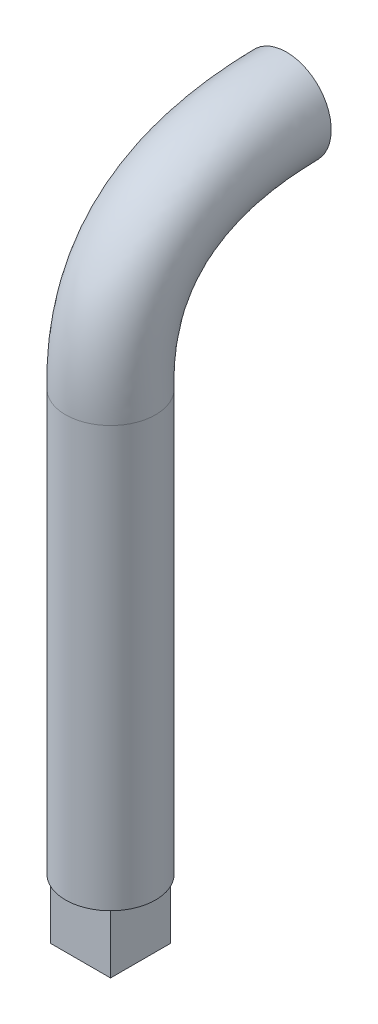
SolidWorks part; units mm, degrees
ref_plane "Front Plane" through (0, 0, 0) normal (0, 0, 1) x (1, 0, 0)
ref_plane "Top Plane" through (0, 0, 0) normal (0, 1, 0) x (1, 0, 0)
ref_plane "Right Plane" through (0, 0, 0) normal (1, 0, 0) x (0, 0, -1)
sketch "Sketch1" plane through (0, 0, 0) normal (0, 1, 0) x (1, 0, 0)
  circle A0 centre (0, 0) radius 7.5
extrude "Boss-Extrude1" add sketch "Sketch1" along normal blind 70
sketch "Sketch2" plane through (0, 0, 0) normal (0, -1, 0) x (1, 0, 0)
  line L1 (-5, 5) -> (5, 5)
  line L2 (-5, 5) -> (-5, -5)
  line L3 (-5, -5) -> (5, -5)
  line L4 (5, 5) -> (5, -5)
  line L5 (-5, 5) -> (5, -5) construction
  line L6 (-5, -5) -> (5, 5) construction
  point P0 (0, 0)
extrude "Boss-Extrude2" add sketch "Sketch2" along normal blind 10
sketch "Sketch3" plane through (0, 0, 0) normal (1, 0, 0) x (0, 0, -1)
  line L0 (7.5, 70) -> (-7.5, 70) construction
  spline S0 degree 2 poles (0, 70) (-0.6718, 95.8831) (29.2595, 96.4198) knots 0 0 0 1 1 1
  point P2 (0, 0)
  point P4 (29.2595, 96.4198)
sketch "Sketch4" plane through (0, 70, 0) normal (0, 1, 0) x (1, 0, 0)
  circle A0 centre (0, 0) radius 7.5
sweep "Sweep1" add profiles "Sketch4" path "Sketch3"
